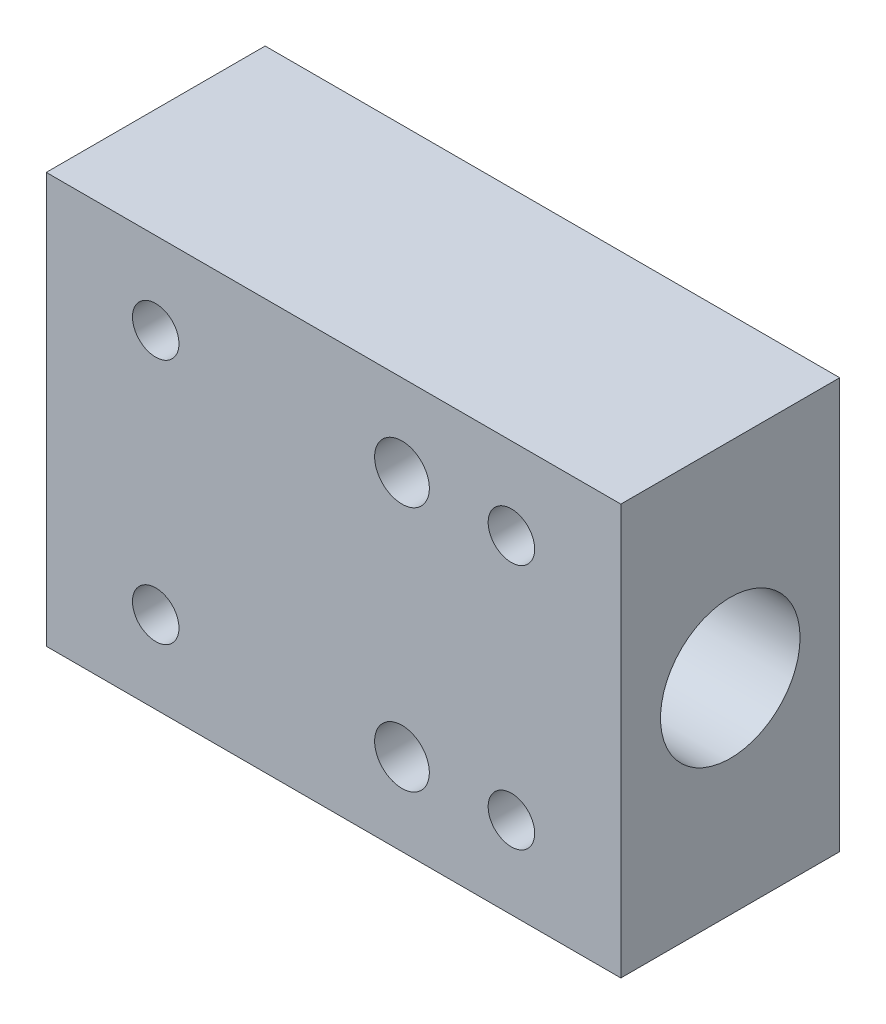
SolidWorks part; units mm, degrees
ref_plane "Alzado" through (0, 0, 0) normal (0, 0, 1) x (1, 0, 0)
ref_plane "Planta" through (0, 0, 0) normal (0, 1, 0) x (1, 0, 0)
ref_plane "Vista lateral" through (0, 0, 0) normal (1, 0, 0) x (0, 0, -1)
sketch "Croquis1" plane through (0, 0, 0) normal (0, 0, 1) x (1, 0, 0)
  line L1 (0, 0) -> (42, 0)
  line L2 (0, 0) -> (0, 30)
  line L3 (0, 30) -> (42, 30)
  line L4 (42, 0) -> (42, 30)
  dimension "D1" = 30
  dimension "D2" = 42
extrude "Saliente-Extruir1" add sketch "Croquis1" along normal blind 16
sketch "Croquis2" plane through (42, 0, 0) normal (1, 0, 0) x (0, 0, -1)
  line L0 (0, 0) -> (0, 30) construction
  line L1 (-16, 0) -> (0, 0) construction
  circle A0 centre (-8, 15) radius 5.1
  dimension "D1" = 10.2
  dimension "D2" = 8
  dimension "D3" = 15
extrude "Cortar-Extruir1" cut sketch "Croquis2" against normal through all
hole_wizard "Refrentado para tornillo con cabeza hueca de M31" positions "Croquis3" profile "Croquis4" counterbore size "M3" standard "DIN" end condition through all
sketch "Croquis3" plane through (0, 0, 0) normal (0, 0, -1) x (-1, 0, 0)
  line L0 (0, 0) -> (-42, 0) construction
  line L1 (-42, 0) -> (-42, 30) construction
  line L2 (0, 30) -> (0, 0) construction
  line L3 (-42, 30) -> (0, 30) construction
  point P0 (-8, 6)
  point P2 (-34, 6)
  point P4 (-34, 24)
  point P6 (-8, 24)
  dimension "D1" = 6
  dimension "D2" = 8
  dimension "D3" = 8
  dimension "D4" = 6
  dimension "D5" = 6
  dimension "D6" = 8
  dimension "D7" = 8
  dimension "D8" = 6
sketch "Croquis4" plane through (8, 6, 0) normal (1, 0, 0) x (0, 1, 0)
  line L0 (0, 0) -> (0, 16)
  line L1 (0, 16) -> (1.7, 16)
  line L3 (1.7, 16) -> (1.7, 3.4)
  line L4 (1.7, 3.4) -> (3.25, 3.4)
  line L5 (3.25, 3.4) -> (3.25, 0)
  line L7 (3.25, 0) -> (0, 0)
  line L11 (0, -6.35) -> (0, 107.95) construction
  dimension "Diámetro de taladro hasta el siguiente" = 3.4
  dimension "Profundidad de taladro hasta el siguiente" = 16
  dimension "Diámetro de refrentado" = 6.5
  dimension "Profundidad de refrentado" = 3.4
hole_wizard "Diámetro de taladro Ø4.0 (4)1" positions "Croquis5" profile "Croquis6" hole size "Ø4.0" standard "DIN" end condition through all
sketch "Croquis5" plane through (0, 0, 0) normal (0, 0, -1) x (-1, 0, 0)
  line L0 (0, 0) -> (-42, 0) construction
  line L1 (-42, 0) -> (-42, 30) construction
  line L2 (-42, 30) -> (0, 30) construction
  point P0 (-26, 6)
  point P2 (-26, 24)
  dimension "D1" = 6
  dimension "D2" = 16
  dimension "D3" = 6
  dimension "D4" = 16
sketch "Croquis6" plane through (26, 6, 0) normal (1, 0, 0) x (0, 1, 0)
  line L0 (0, 0) -> (0, 16)
  line L1 (0, 16) -> (2, 16)
  line L2 (2, 16) -> (2, 0)
  line L5 (2, 0) -> (0, 0)
  line L11 (0, -6.35) -> (0, 107.95) construction
  dimension "Diámetro de taladro hasta el siguiente" = 4
  dimension "Profundidad de taladro hasta el siguiente" = 16
